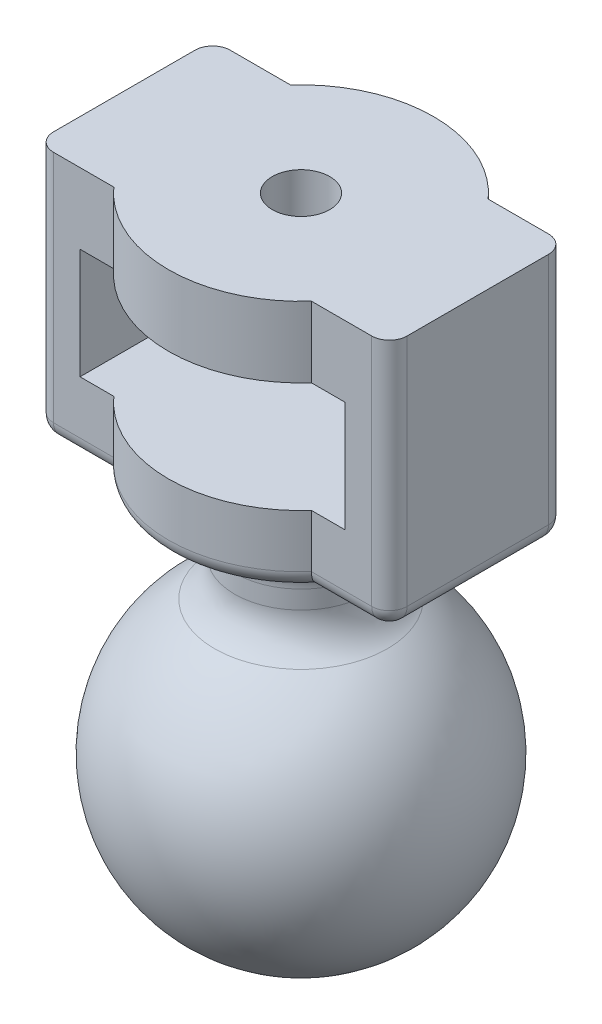
SolidWorks part; units mm, degrees
ref_plane "Front Plane" through (0, 0, 0) normal (0, 0, 1) x (1, 0, 0)
ref_plane "Top Plane" through (0, 0, 0) normal (0, 1, 0) x (1, 0, 0)
ref_plane "Right Plane" through (0, 0, 0) normal (1, 0, 0) x (0, 0, -1)
sketch "Sketch1" plane through (0, 0, 0) normal (0, 1, 0) x (1, 0, 0)
  line L1 (-20, 10) -> (20, 10)
  line L2 (-20, 10) -> (-20, -10)
  line L3 (-20, -10) -> (20, -10)
  line L4 (20, 10) -> (20, -10)
  line L5 (-20, 10) -> (20, -10) construction
  line L6 (-20, -10) -> (20, 10) construction
  line L7 (-15, 10) -> (15, 10)
  line L8 (-15, 10) -> (-15, -10)
  line L9 (-15, -10) -> (15, -10)
  line L10 (15, 10) -> (15, -10)
  line L11 (-15, 10) -> (15, -10) construction
  line L12 (-15, -10) -> (15, 10) construction
  circle A0 centre (0, 0) radius 15
  circle A1 centre (0, 0) radius 3.25
  dimension "D1" = 30
  dimension "D2" = 6.5
  dimension "D3" = 20
  dimension "D4" = 40
extrude "Boss-Extrude1" add sketch "Sketch1" along normal blind 8 contours A0 L3 L4 L1 | A0 L1 L2 L3 | L1 A0 | L3 A0 L1 A1 | L3 A0 | L8 L7 L10 L9 | A1 region at (-17.5, 0, 0) region at (0, 0, -12.0316) region at (0, 0, -9.6394) region at (0, 0, 12.0316) region at (17.5, 0, 0)
extrude "Boss-Extrude2" add sketch "Sketch1<3>" against normal blind 12.5 contours L8 L1 L2 L3 | L1 L10 L3 L4 region at (-17.5, 0, 0) region at (17.5, 0, 0)
sketch "Sketch1<3>" plane through (0, 0, 0) normal (0, 1, 0) x (1, 0, 0) same geometry as "Sketch1"
extrude "Boss-Extrude3" add sketch "Sketch1<4>" against normal blind 8 from surface contours L9 A0 | L9 A0 L7 A1 | L7 A0 | A0 L10 L1 | L1 L10 L3 L4 | L8 L1 L2 L3 | L3 L4 L1 L2 region at (-17.5, 0, 0) region at (0, 0, -12.0316) region at (0, 0, -9.6394) region at (13.8843, 0, -7.5681) region at (0, 0, 12.0316) region at (17.5, 0, 0) starting at face at (-17.5, -12.5, 0)
sketch "Sketch1<4>" plane through (0, 0, 0) normal (0, 1, 0) x (1, 0, 0) same geometry as "Sketch1"
sketch "Sketch2" plane through (0, -20.5, 0) normal (0, -1, 0) x (1, 0, 0)
  circle A0 centre (0, 0) radius 7.5
  dimension "D1" = 15
extrude "Boss-Extrude4" add sketch "Sketch2" along normal blind 10
sketch "Sketch3" plane through (0, 0, 0) normal (0, 0, 1) x (1, 0, 0)
  line L0 (-7.5, -30.5) -> (7.5, -30.5) construction
  line L1 (-7.5, -30.5) -> (7.5, -30.5)
  line L2 (0, -64.8631) -> (0, -28.8631) construction
  arc A0 (0, -28.8631) -> (0, -64.8631) centre (0, -46.8631) ccw
  point P6 (0, -30.5)
  dimension "D1" = 36
revolve "Revolve1" add sketch "Sketch3" angle 360 about L2 region at (-7.7188, -47.1439, 0)
fillet "Fillet2" radius 2 12 edges at (-20, -6.25, 10) (-20, -6.25, -10) (20, -6.25, -10) (20, -6.25, 10) (15.5902, -20.5, 10) (0, -20.5, 15) (-15.5902, -20.5, 10) (-20, -20.5, 0) (-15.5902, -20.5, -10) (0, -20.5, -15) (15.5902, -20.5, -10) (20, -20.5, 0)
fillet "Fillet3" radius 5 2 edges at (0, -30.5, -7.5) (0, -20.5, -7.5)
